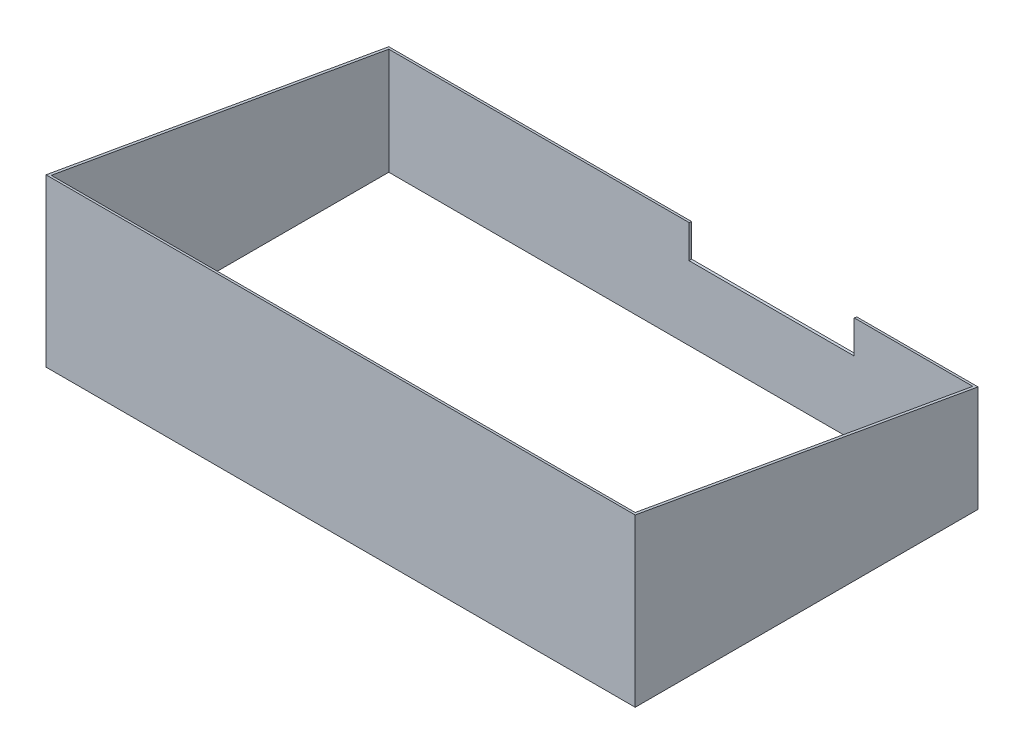
SolidWorks part; units mm, degrees
material "Particle Board"
ref_plane "Front Plane" through (0, 0, 0) normal (0, 0, 1) x (1, 0, 0)
ref_plane "Top Plane" through (0, 0, 0) normal (0, 1, 0) x (1, 0, 0)
ref_plane "Right Plane" through (0, 0, 0) normal (1, 0, 0) x (0, 0, -1)
sketch "Sketch1" plane through (0, 0, 0) normal (1, 0, 0) x (0, 0, -1)
  line L0 (0, 403.3854) -> (0, 0)
  line L1 (0, 0) -> (830.1929, 0)
  line L4 (830.1929, 0) -> (830.1929, 257)
  line L5 (0, 403.3854) -> (830.1929, 257)
  dimension "D1" = 10
  dimension "D2" = 843
  dimension "D3" = 257
extrude "Boss-Extrude1" add sketch "Sketch1" along normal blind 713.5 and the other way blind 713.5
shell "Shell1" thickness 6.35 removed face at (0, 0, -415.0965) removed face at (0, 330.1927, -415.0965)
sketch "Sketch3" plane through (0, 0, -823.8429) normal (0, 0, 1) x (1, 0, 0)
  line L1 (20, 268.1197) -> (420, 268.1197)
  line L2 (20, 268.1197) -> (20, 178.1197)
  line L3 (20, 178.1197) -> (420, 178.1197)
  line L4 (420, 268.1197) -> (420, 178.1197)
  line L5 (707.15, 258.1197) -> (-707.15, 258.1197) construction
  line L7 (0, -55) -> (0, 55) construction
  dimension "D1" = 20
  dimension "D2" = 400
  dimension "D3" = 10
  dimension "D4" = 80
extrude "Cut-Extrude2" cut sketch "Sketch3" against normal up to next
sketch "Sketch4" plane through (-713.5, 0, 0) normal (-1, 0, 0) x (0, 0, 1)
  line L1 (-158.5, 32) -> (-251.5, 32)
  line L2 (-158.5, 32) -> (-158.5, 134)
  line L3 (-158.5, 134) -> (-251.5, 134)
  line L4 (-251.5, 32) -> (-251.5, 134)
  dimension "D1" = 93
  dimension "D2" = 102
  dimension "D3" = 158.5
  dimension "D4" = 32
extrude "Cut-Extrude3" cut sketch "Sketch4" against normal up to next
